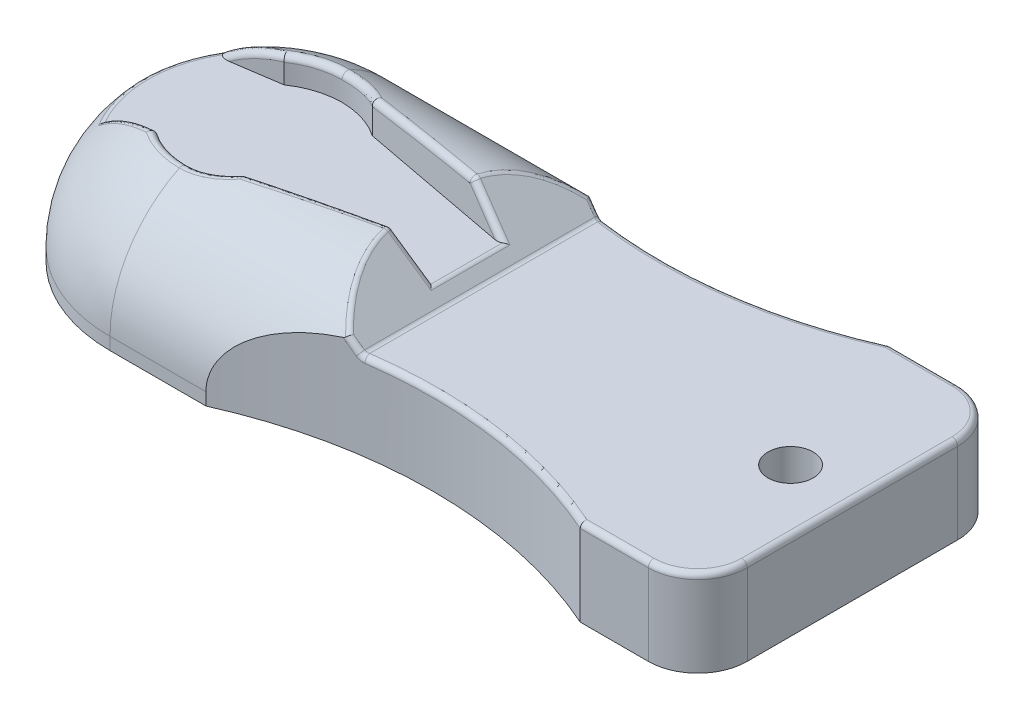
SolidWorks part; units mm, degrees
ref_plane "Front Plane" through (0, 0, 0) normal (0, 0, 1) x (1, 0, 0)
ref_plane "Top Plane" through (0, 0, 0) normal (0, 1, 0) x (1, 0, 0)
ref_plane "Right Plane" through (0, 0, 0) normal (1, 0, 0) x (0, 0, -1)
sketch "Sketch1" plane through (0, 0, 0) normal (0, 1, 0) x (1, 0, 0)
  line L1 (-30, 12.5) -> (30, 12.5)
  line L2 (-30, 12.5) -> (-30, -12.5)
  line L3 (-30, -12.5) -> (30, -12.5)
  line L4 (30, 12.5) -> (30, -12.5)
  dimension "D1" = 60
  dimension "D2" = 30
  dimension "D3" = 25
  dimension "D4" = 12.5
extrude "Boss-Extrude1" add sketch "Sketch1" along normal blind 11
sketch "Sketch2" plane through (0, 11, 0) normal (0, 1, 0) x (1, 0, 0)
  line L0 (30, 12.5) -> (-30, 12.5) construction
  line L6 (-30, -12.5) -> (30, -12.5) construction
  line L7 (0, -12.5) -> (30, -12.5)
  line L8 (30, -12.5) -> (30, 12.5)
  line L9 (30, 12.5) -> (0, 12.5)
  line L13 (0, 12.5) -> (0, -12.5)
extrude "Cut-Extrude1" cut sketch "Sketch2" against normal blind 4
sketch "Sketch3" plane through (0, 11, 0) normal (0, 1, 0) x (1, 0, 0)
  line L0 (0, -2.5) -> (-13.939, -5.1363)
  line L5 (-30, -12.5) -> (0, -12.5) construction
  line L6 (-30, 12.5) -> (-30, -12.5) construction
  line L8 (-13.939, 5.1363) -> (0, 2.5)
  line L10 (-21.061, 5.1363) -> (-26.5201, 4.3171)
  line L11 (-26.5201, -4.3171) -> (-21.061, -5.1363)
  arc A0 (-13.939, 5.1363) -> (-21.061, 5.1363) centre (-17.5, 0) ccw
  arc A1 (0, -2.5) -> (0, 2.5) centre (0, 0) ccw
  arc A3 (-21.061, -5.1363) -> (-13.939, -5.1363) centre (-17.5, 0) ccw
  arc A4 (-26.5201, 4.3171) -> (-26.5201, -4.3171) centre (-17.5, 0) ccw
  point P4 (-14.939, 5.7012)
  point P5 (-27.5, 0)
  dimension "D2" = 5
  dimension "D3" = 12.5
  dimension "D4" = 17.5
  dimension "D5" = 12.5
  dimension "D6" = 12.5
  dimension "D7" = 9.0201
  dimension "D8" = 9.0201
  dimension "D9" = 12.5
  dimension "D10" = 10
  dimension "D11" = 13.939
  dimension "D12" = 13.939
  dimension "D13" = 5.4591
  dimension "D14" = 5.4591
extrude "Cut-Extrude2" cut sketch "Sketch3" against normal blind 3
fillet "Fillet1" 2 edges at (-30, 5.5, 12.5) (-30, 5.5, -12.5) type full round first side face at (0, 6, 12.5) second side face at (0, 6, -12.5) middle face at (-30, 5.5, 0)
chamfer "Chamfer2" distance 4 2 edges at (0, 11, -7.5) (0, 11, 7.5)
fillet "Fillet3" radius 4 2 edges at (30, 3.5, -12.5) (30, 3.5, 12.5)
sketch "Sketch6" plane through (0, 7, 0) normal (0, 1, 0) x (1, 0, 0)
  line L0 (26, 12.5) -> (0, 12.5) construction
  line L1 (30, -8.5) -> (30, 8.5) construction
  circle A0 centre (25, 0) radius 1.825
  dimension "D1" = 3.65
  dimension "D2" = 12.5
  dimension "D3" = 5
sketch "Sketch8" plane through (0, 0, 0) normal (0, -1, 0) x (1, 0, 0)
  circle A0 centre (-17.5, 0) radius 6.45
  arc A2 (-17.5, 12.5) -> (-17.5, -12.5) centre (-17.5, 0) ccw construction
  point P8 (-30, 0)
  dimension "D3" = 12.9
  dimension "D1" = 0
  dimension "D2" = 12.5
extrude "Cut-Extrude5" cut sketch "Sketch8" against normal blind 3.6
extrude "Cut-Extrude7" cut sketch "Sketch6" against normal through all
sketch "Sketch10" plane through (0, 0, 0) normal (0, -1, 0) x (1, 0, 0)
  line L0 (-17.5, 12.5) -> (26, 12.5) construction
  line L1 (26, -12.5) -> (-17.5, -12.5) construction
  line L2 (-9.75, 12.5) -> (20.5, 12.5)
  line L3 (-9.75, -12.5) -> (20.5, -12.5)
  arc A0 (-9.75, 12.5) -> (20.5, 12.5) centre (5.375, 46.5411) ccw
  arc A1 (-9.75, -12.5) -> (20.5, -12.5) centre (5.375, -46.5411) cw
  dimension "D5" = 37.25
  dimension "D6" = 37.25
  dimension "D1" = 9.75
  dimension "D2" = 9.75
  dimension "D3" = 20.5
  dimension "D4" = 20.5
extrude "Cut-Extrude8" cut sketch "Sketch10" against normal through all
fillet "Fillet4" radius 10 3 edges at (-13.625, 11, -12.5) (-13.625, 11, 12.5) (-30, 11, 0)
fillet "Fillet5" radius 0.45 24 edges at (-15.4999, 10.3965, 5.9213) (-15.7904, 10.3631, -6.0116) (23.25, 7, 12.5) (28.8284, 7, 11.3284) (30, 7, 0) (28.8284, 7, -11.3284) (0, 7, 0) (-0.412, 7.412, 9.7434) (-3.0152, 10.0152, 6.8273) (-2.4859, 9.4859, 2.9702) (-1, 8, 0) (-2.4859, 9.4859, -2.9702) (-3.0152, 10.0152, -6.8273) (-0.412, 7.412, -9.7434) (-27.1414, 8, 0) (-23.6678, 9.4913, 4.7452) (-19.3655, 10.2702, 5.9651) (-19.3655, 10.2702, -5.9651) (-24.1425, 9.27, -4.6739) (23.25, 7, -12.5) (10.4497, 7, -9.6384) (10.4497, 7, 9.6384) (-8.9966, 10.8542, 4.2016) (-8.9966, 10.8542, -4.2016)
